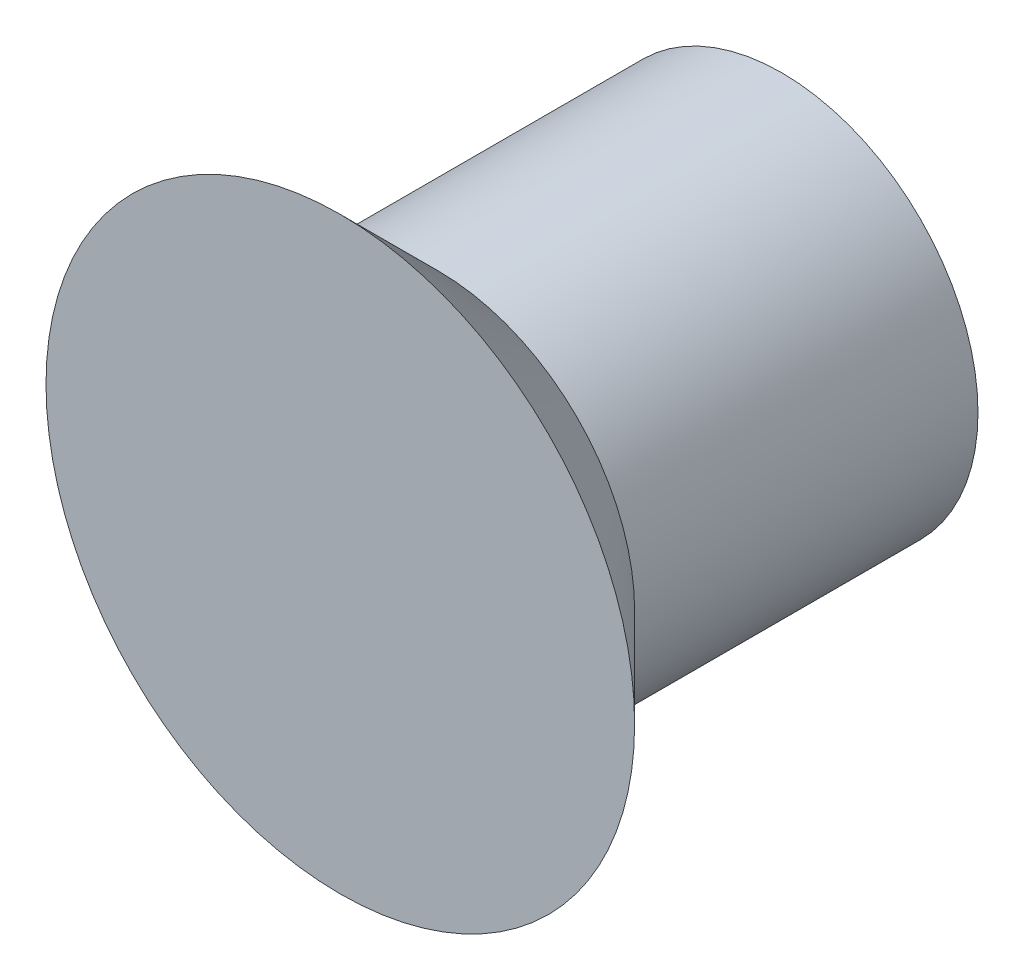
SolidWorks part; units mm, degrees
ref_plane "Ön Düzlem" through (0, 0, 0) normal (0, 0, 1) x (1, 0, 0)
ref_plane "Üst Düzlem" through (0, 0, 0) normal (0, 1, 0) x (1, 0, 0)
ref_plane "Sağ Düzlem" through (0, 0, 0) normal (1, 0, 0) x (0, 0, -1)
sketch "Çizim1" plane through (0, 0, 0) normal (0, 0, 1) x (1, 0, 0)
  circle A0 centre (0, 0) radius 2
  dimension "D1" = 4
extrude "Yükseklik-Ekstrüzyon1" add sketch "Çizim1" along normal blind 3.5
sketch "Çizim3" plane through (0, 0, 3.5) normal (0, 0, 1) x (1, 0, 0)
  circle A0 centre (0, 0) radius 2
  dimension "D1" = 4
extrude "Yükseklik-Ekstrüzyon3" add sketch "Çizim3" along normal blind 1 draft 45 draft outward yes
